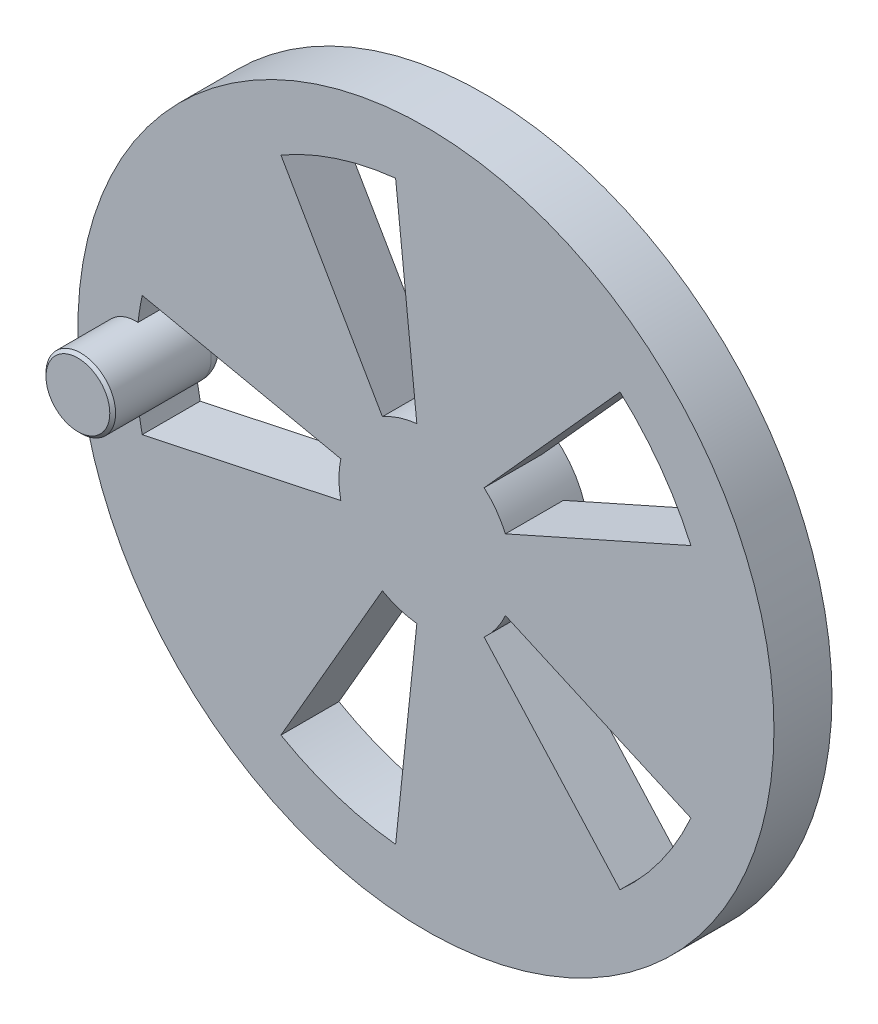
SolidWorks part; units mm, degrees
ref_plane "Front Plane" through (0, 0, 0) normal (0, 0, 1) x (1, 0, 0)
ref_plane "Top Plane" through (0, 0, 0) normal (0, 1, 0) x (1, 0, 0)
ref_plane "Right Plane" through (0, 0, 0) normal (1, 0, 0) x (0, 0, -1)
sketch "Sketch1" plane through (0, 0, 0) normal (0, 0, 1) x (1, 0, 0)
  line L0 (0, 0) -> (-50, 0)
  circle A0 centre (0, 0) radius 60
  circle A1 centre (-50, 0) radius 6
  dimension "D1" = 120
  dimension "D3" = 12
  dimension "D2" = 50
extrude "Boss-Extrude1" add sketch "Sketch1" against normal blind 10 contours A0
extrude "Boss-Extrude2" add sketch "Sketch1<3>" along normal blind 10 contours A1 region at (-55.8303, 0, 0)
sketch "Sketch1<3>" plane through (0, 0, 0) normal (0, 0, 1) x (1, 0, 0) same geometry as "Sketch1"
sketch "Sketch2" plane through (0, 0, 0) normal (0, 0, 1) x (1, 0, 0)
  line L0 (-15, 0) -> (-50, 0)
  line L1 (0, 0) -> (-48.9074, 10.3956)
  line L2 (0, 0) -> (-48.9074, -10.3956)
  line L3 (0, 0) -> (-5.2264, 49.7261)
  line L4 (0, 0) -> (-25, 43.3013)
  line L5 (0, 0) -> (45.6773, 20.3368)
  line L6 (0, 0) -> (33.4565, 37.1572)
  line L7 (0, 0) -> (33.4565, -37.1572)
  line L8 (0, 0) -> (45.6773, -20.3368)
  line L9 (0, 0) -> (-25, -43.3013)
  line L10 (0, 0) -> (-5.2264, -49.7261)
  circle A0 centre (0, 0) radius 50
  circle A1 centre (0, 0) radius 15
  point P19 (0, 0)
  circle M2 centre (-50, 0) radius 6
  dimension "D1" = 30
  dimension "D2" = 12
  dimension "D3" = 5
extrude "Cut-Extrude1" cut sketch "Sketch2" against normal blind 10 contours A1 L0 A0 L2 M2 | A1 L1 A0 L0 M2 | A1 L3 A0 L4 | A1 L5 A0 L6 | A1 L7 A0 L8 | A1 L9 A0 L10 region at (-33.8105, -3.8787, 0) region at (-33.8105, 3.8787, 0) region at (-10.9333, 33.6494, 0) region at (-10.9333, -33.6494, 0) region at (28.6239, 20.7964, 0) region at (28.6239, -20.7964, 0)
sketch "Sketch3" plane through (0, 0, -10) normal (0, 0, -1) x (-1, 0, 0)
  circle A0 centre (0, 0) radius 10
  circle A1 centre (0, 0) radius 15
  dimension "D1" = 20
extrude "Boss-Extrude4" add sketch "Sketch3" along normal blind 3
fillet "Fillet1" radius 3 1 edges at (-44, 0, -10)
chamfer "Chamfer1" distance 0.5 angle 45 1 edges at (-44, 0, 10)
